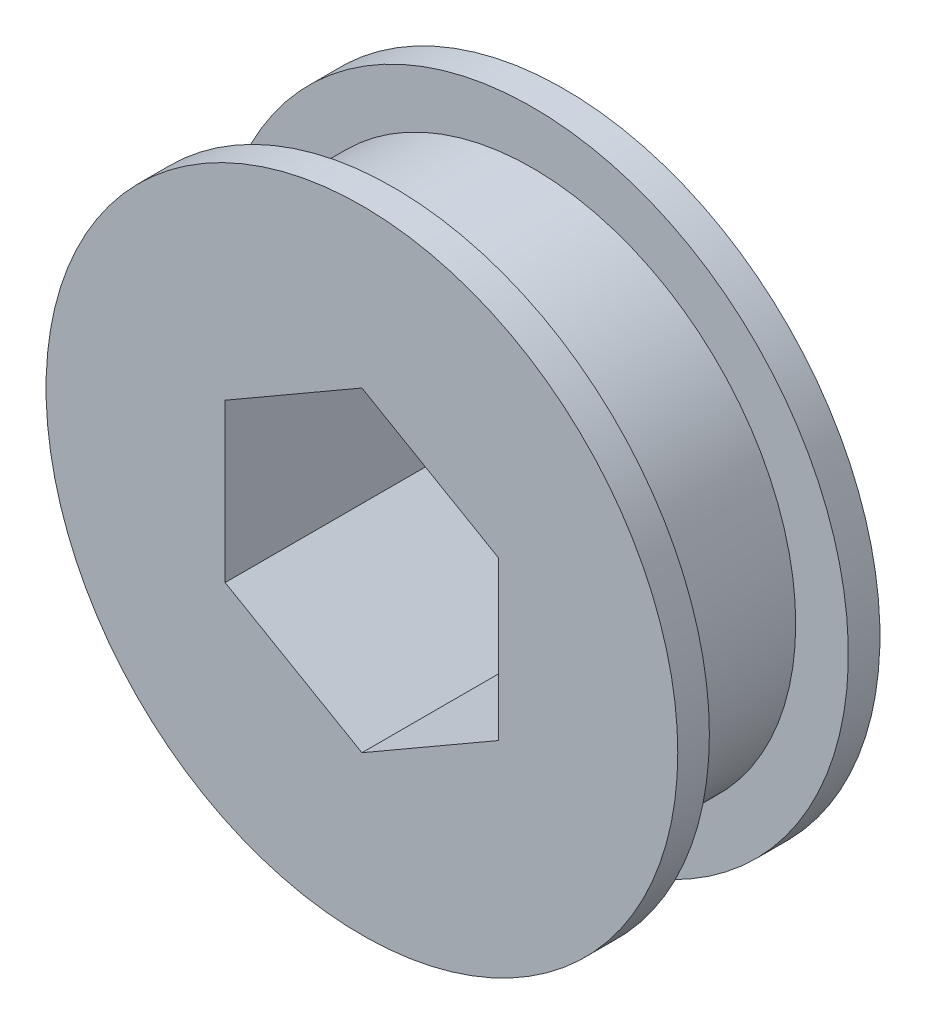
SolidWorks part; units mm, degrees
ref_plane "Front Plane" through (0, 0, 0) normal (0, 0, 1) x (1, 0, 0)
ref_plane "Top Plane" through (0, 0, 0) normal (0, 1, 0) x (1, 0, 0)
ref_plane "Right Plane" through (0, 0, 0) normal (1, 0, 0) x (0, 0, -1)
sketch "Sketch1" plane through (0, 0, 0) normal (0, 0, 1) x (1, 0, 0)
  circle A0 centre (0, 0) radius 12.5
  dimension "D1" = 25
extrude "Boss-Extrude1" add sketch "Sketch1" along normal mid plane 6.6
sketch "Sketch2" plane through (0, 0, -3.3) normal (0, 0, -1) x (-1, 0, 0)
  circle A0 centre (0, 0) radius 15
  dimension "D1" = 30
extrude "Boss-Extrude2" add sketch "Sketch2" along normal blind 1.5
sketch "Sketch3" plane through (0, 0, 3.3) normal (0, 0, 1) x (1, 0, 0)
  circle A0 centre (0, 0) radius 15
  dimension "D1" = 30
extrude "Boss-Extrude3" add sketch "Sketch3" along normal blind 1.5
sketch "Sketch4" plane through (0, 0, 4.8) normal (0, 0, 1) x (1, 0, 0)
  line L1 (0, 7.5) -> (-6.4952, 3.75)
  line L2 (-6.4952, 3.75) -> (-6.4952, -3.75)
  line L3 (-6.4952, -3.75) -> (0, -7.5)
  line L4 (0, -7.5) -> (6.4952, -3.75)
  line L5 (6.4952, -3.75) -> (6.4952, 3.75)
  line L6 (6.4952, 3.75) -> (0, 7.5)
  circle A0 centre (0, 0) radius 6.4952 construction
  dimension "D1" = 15
extrude "Cut-Extrude1" cut sketch "Sketch4" against normal through all both and the other way through all
